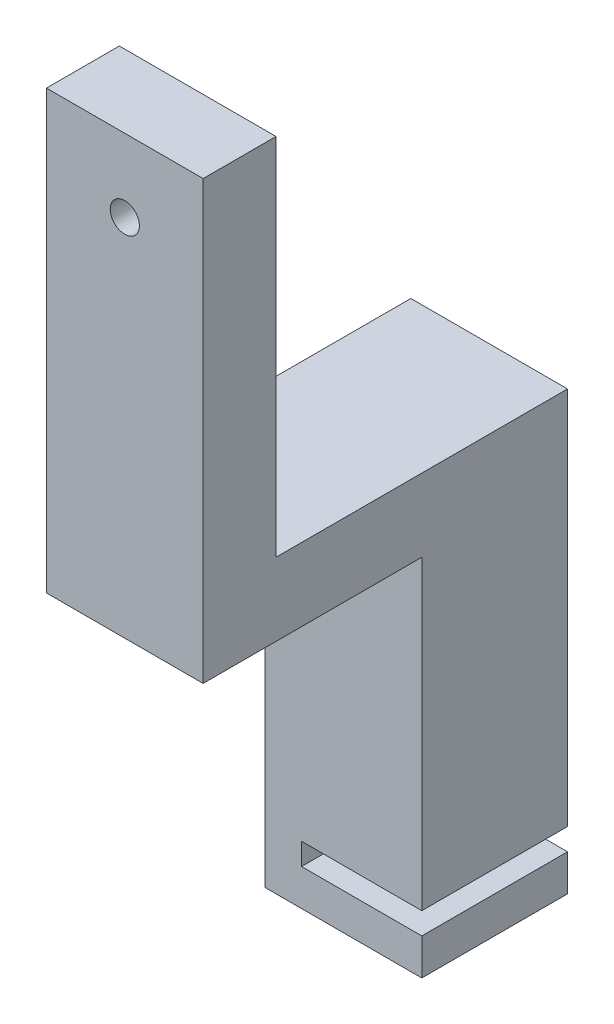
SolidWorks part; units mm, degrees
ref_plane "Front Plane" through (0, 0, 0) normal (0, 0, 1) x (1, 0, 0)
ref_plane "Top Plane" through (0, 0, 0) normal (0, 1, 0) x (1, 0, 0)
ref_plane "Right Plane" through (0, 0, 0) normal (1, 0, 0) x (0, 0, -1)
sketch "Sketch1" plane through (0, 0, 0) normal (0, 0, 1) x (1, 0, 0)
  line L0 (0, 8) -> (0, 50)
  line L1 (0, 0) -> (-21.5, 0)
  line L2 (0, 0) -> (0, 5)
  line L3 (0, 50) -> (-21.5, 50) construction
  line L4 (-21.5, 0) -> (-21.5, 50)
  line L5 (0, 8) -> (-16.5, 8)
  line L7 (0, 5) -> (-16.5, 5)
  line L8 (-16.5, 8) -> (-16.5, 5)
  line L11 (-21.5, 50) -> (-21.5, 110)
  line L12 (-21.5, 110) -> (0, 110)
  line L13 (0, 50) -> (0, 110)
  dimension "D1" = 21.5
  dimension "D2" = 16.5
  dimension "D3" = 3
  dimension "D4" = 5
  dimension "D5" = 50
  dimension "D6" = 60
extrude "Boss-Extrude1" add sketch "Sketch1" along normal blind 20
extrude "Boss-Extrude2" add sketch "Sketch1<2>" along normal blind 50 contours L3 L13 L12 L11 region at (-10.75, 80, 0)
sketch "Sketch1<2>" plane through (0, 0, 0) normal (0, 0, 1) x (1, 0, 0) same geometry as "Sketch1"
sketch "Sketch3" plane through (0, 0, 0) normal (1, 0, 0) x (0, 0, -1)
  line L0 (-50, 50) -> (-50, 110) construction
  line L1 (0, 110) -> (-40, 110)
  line L2 (0, 110) -> (0, 60)
  line L3 (0, 60) -> (-40, 60)
  line L4 (-40, 110) -> (-40, 60)
  line L5 (-50, 50) -> (-20, 50) construction
  dimension "D1" = 10
  dimension "D2" = 10
extrude "Cut-Extrude1" cut sketch "Sketch3" against normal blind 50
sketch "Sketch4" plane through (0, 0, 40) normal (0, 0, -1) x (-1, 0, 0)
  line L0 (10.75, 110) -> (10.75, 60) construction
  line L1 (21.5, 110) -> (0, 110) construction
  line L2 (21.5, 60) -> (0, 60) construction
  circle A0 centre (10.75, 100) radius 2
  point P8 (0, 0)
  dimension "D1" = 4
  dimension "D2" = 10
extrude "Cut-Extrude2" cut sketch "Sketch4" against normal blind 50
